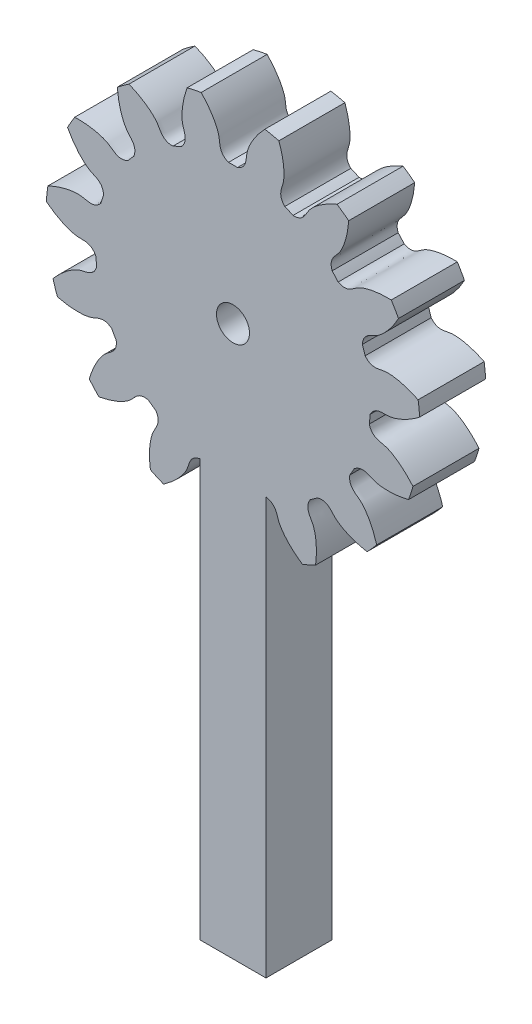
SolidWorks part; units mm, degrees
ref_plane "前视基准面" through (0, 0, 0) normal (0, 0, 1) x (1, 0, 0)
ref_plane "上视基准面" through (0, 0, 0) normal (0, 1, 0) x (1, 0, 0)
ref_plane "右视基准面" through (0, 0, 0) normal (1, 0, 0) x (0, 0, -1)
sketch "草图1" plane through (0, 0, 0) normal (0, 0, 1) x (1, 0, 0)
  circle A0 centre (0, 0) radius 17
extrude "凸台-拉伸1" add sketch "草图1" along normal blind 30
ref_axis "基准轴1" through (0, 0, -1.5) along (0, 0, 1)
sketch "草图2" plane through (0, 0, 0) normal (0, 0, 1) x (1, 0, 0)
  line L0 (0, 0) -> (0, 17) construction
  circle A0 centre (0, 0) radius 17 construction
  arc A1 (0.4086, 12.4933) -> (-0.4086, 12.4933) centre (0, 0) ccw
  arc A2 (6.4937, 19.2719) -> (-6.4937, 19.2719) centre (0, 0) ccw
  spline S0 degree 3 poles (0.4086, 12.4933) (1.3144, 12.8688) (1.1442, 13.5727) (1.3025, 14.217) (1.3149, 14.2633) (1.3297, 14.3148) (1.3472, 14.3713) (1.3676, 14.4329) (1.3912, 14.4993) (1.418, 14.5705) (1.4484, 14.6465) (1.4824, 14.7269) (1.5204, 14.8119) (1.5624, 14.9011) (1.6088, 14.9946) (1.6596, 15.0921) (1.715, 15.1935) (1.7753, 15.2987) (1.8405, 15.4075) (1.9109, 15.5198) (1.9867, 15.6353) (2.0679, 15.754) (2.1547, 15.8755) (2.2473, 15.9999) (2.3459, 16.1268) (2.4505, 16.2561) (2.5613, 16.3877) (2.6784, 16.5212) (2.802, 16.6565) (2.9322, 16.7934) (3.069, 16.9316) (3.2126, 17.0711) (3.3631, 17.2115) (3.5206, 17.3526) (3.6851, 17.4942) (3.8568, 17.6361) (4.0357, 17.778) (4.2219, 17.9197) (4.4154, 18.061) (4.6163, 18.2017) (4.8247, 18.3414) (5.0406, 18.48) (5.2641, 18.6172) (5.4951, 18.7527) (5.7336, 18.8864) (6.0652, 19.0635) (6.3203, 19.1901) (6.4937, 19.2719) knots 0 0 0 0 0.202473 0.206979 0.212085 0.217793 0.224101 0.23101 0.23852 0.24663 0.255341 0.264653 0.274566 0.285079 0.296194 0.307909 0.320225 0.333141 0.346659 0.360777 0.375496 0.390816 0.406736 0.423257 0.440379 0.458102 0.476426 0.49535 0.514875 0.535001 0.555728 0.577055 0.598984 0.621513 0.644642 0.668373 0.692704 0.717636 0.743169 0.769303 0.796037 0.823373 0.851309 0.879845 0.908983 0.938721 1 1 1 1
  spline S1 degree 3 poles (-0.4086, 12.4933) (-1.3144, 12.8688) (-1.1442, 13.5727) (-1.3025, 14.217) (-1.3149, 14.2633) (-1.3297, 14.3148) (-1.3472, 14.3713) (-1.3676, 14.4329) (-1.3912, 14.4993) (-1.418, 14.5705) (-1.4484, 14.6465) (-1.4824, 14.7269) (-1.5204, 14.8119) (-1.5624, 14.9011) (-1.6088, 14.9946) (-1.6596, 15.0921) (-1.715, 15.1935) (-1.7753, 15.2987) (-1.8405, 15.4075) (-1.9109, 15.5198) (-1.9867, 15.6353) (-2.0679, 15.754) (-2.1547, 15.8755) (-2.2473, 15.9999) (-2.3459, 16.1268) (-2.4505, 16.2561) (-2.5613, 16.3877) (-2.6784, 16.5212) (-2.802, 16.6565) (-2.9322, 16.7934) (-3.069, 16.9316) (-3.2126, 17.0711) (-3.3631, 17.2115) (-3.5206, 17.3526) (-3.6851, 17.4942) (-3.8568, 17.6361) (-4.0357, 17.778) (-4.2219, 17.9197) (-4.4154, 18.061) (-4.6163, 18.2017) (-4.8247, 18.3414) (-5.0406, 18.48) (-5.2641, 18.6172) (-5.4951, 18.7527) (-5.7336, 18.8864) (-6.0652, 19.0635) (-6.3203, 19.1901) (-6.4937, 19.2719) knots 0 0 0 0 0.202473 0.206979 0.212085 0.217793 0.224101 0.23101 0.23852 0.24663 0.255341 0.264653 0.274566 0.285079 0.296194 0.307909 0.320225 0.333141 0.346659 0.360777 0.375496 0.390816 0.406736 0.423257 0.440379 0.458102 0.476426 0.49535 0.514875 0.535001 0.555728 0.577055 0.598984 0.621513 0.644642 0.668373 0.692704 0.717636 0.743169 0.769303 0.796037 0.823373 0.851309 0.879845 0.908983 0.938721 1 1 1 1
extrude "切除-拉伸1" cut sketch "草图2" along normal through all
pattern_circular "阵列(圆周)1" count 15 every 24 about axis through (0, 0, -1.5) along (0, 0, 1) of "切除-拉伸1"
sketch "草图3" plane through (0, 0, 0) normal (0, 0, 1) x (1, 0, 0)
  circle A0 centre (0, 0) radius 15 construction
  dimension "Dn" = 30
sketch "草图4" plane through (0, 0, 30) normal (0, 0, 1) x (1, 0, 0)
  arc A30 (-4.7082, 11.5794) -> (-5.4547, 11.247) centre (0, 0) ccw
  arc A31 (-9.4567, 14.127) -> (-10.5132, 13.3593) centre (0, 0) ccw
  arc A32 (-9.011, 8.6633) -> (-9.5577, 8.056) centre (0, 0) ccw
  arc A33 (-14.3851, 9.0592) -> (-15.0381, 7.9282) centre (0, 0) ccw
  arc A34 (-11.7556, 4.2492) -> (-12.0081, 3.4721) centre (0, 0) ccw
  arc A35 (-16.8261, 2.4251) -> (-16.9627, 1.1263) centre (0, 0) ccw
  arc A36 (-12.4676, -0.8996) -> (-12.3822, -1.7122) centre (0, 0) ccw
  arc A37 (-16.3578, -4.6284) -> (-15.9542, -5.8704) centre (0, 0) ccw
  arc A38 (-11.0238, -5.8928) -> (-10.6152, -6.6005) centre (0, 0) ccw
  arc A39 (-13.0611, -10.8816) -> (-12.1872, -11.8521) centre (0, 0) ccw
  arc A40 (-7.6739, -9.8672) -> (-7.0128, -10.3475) centre (0, 0) ccw
  arc A41 (-7.5059, -15.2532) -> (-6.3129, -15.7844) centre (0, 0) ccw
  arc A42 (-2.9971, -12.1354) -> (-2.1979, -12.3053) centre (0, 0) ccw
  arc A43 (-0.653, -16.9875) -> (0.653, -16.9875) centre (0, 0) ccw
  arc A44 (2.1979, -12.3053) -> (2.9971, -12.1354) centre (0, 0) ccw
  arc A45 (6.3129, -15.7844) -> (7.5059, -15.2532) centre (0, 0) ccw
  arc A46 (7.0128, -10.3475) -> (7.6739, -9.8672) centre (0, 0) ccw
  arc A47 (12.1872, -11.8521) -> (13.0611, -10.8816) centre (0, 0) ccw
  arc A48 (10.6152, -6.6005) -> (11.0238, -5.8928) centre (0, 0) ccw
  arc A49 (15.9542, -5.8704) -> (16.3578, -4.6284) centre (0, 0) ccw
  arc A50 (12.3822, -1.7122) -> (12.4676, -0.8996) centre (0, 0) ccw
  arc A51 (16.9627, 1.1263) -> (16.8261, 2.4251) centre (0, 0) ccw
  arc A52 (12.0081, 3.4721) -> (11.7556, 4.2492) centre (0, 0) ccw
  arc A53 (15.0381, 7.9282) -> (14.3851, 9.0592) centre (0, 0) ccw
  arc A54 (9.5577, 8.056) -> (9.011, 8.6633) centre (0, 0) ccw
  arc A55 (10.5132, 13.3593) -> (9.4567, 14.127) centre (0, 0) ccw
  arc A56 (5.4547, 11.247) -> (4.7082, 11.5794) centre (0, 0) ccw
  arc A57 (4.1706, 16.4805) -> (2.8932, 16.752) centre (0, 0) ccw
  arc A58 (0.4086, 12.4933) -> (-0.4086, 12.4933) centre (0, 0) ccw
  arc A59 (-2.8932, 16.752) -> (-4.1706, 16.4805) centre (0, 0) ccw
  arc A60 (-4.7082, 11.5794) -> (-5.4547, 11.247) centre (0, 0) ccw
  arc A61 (-9.4567, 14.127) -> (-10.5132, 13.3593) centre (0, 0) ccw
  arc A62 (-9.011, 8.6633) -> (-9.5577, 8.056) centre (0, 0) ccw
  arc A63 (-14.3851, 9.0592) -> (-15.0381, 7.9282) centre (0, 0) ccw
  arc A64 (-11.7556, 4.2492) -> (-12.0081, 3.4721) centre (0, 0) ccw
  arc A65 (-16.8261, 2.4251) -> (-16.9627, 1.1263) centre (0, 0) ccw
  arc A66 (-12.4676, -0.8996) -> (-12.3822, -1.7122) centre (0, 0) ccw
  arc A67 (-16.3578, -4.6284) -> (-15.9542, -5.8704) centre (0, 0) ccw
  arc A68 (-11.0238, -5.8928) -> (-10.6152, -6.6005) centre (0, 0) ccw
  arc A69 (-13.0611, -10.8816) -> (-12.1872, -11.8521) centre (0, 0) ccw
  arc A70 (-7.6739, -9.8672) -> (-7.0128, -10.3475) centre (0, 0) ccw
  arc A71 (-7.5059, -15.2532) -> (-6.3129, -15.7844) centre (0, 0) ccw
  arc A72 (-2.9971, -12.1354) -> (-2.1979, -12.3053) centre (0, 0) ccw
  arc A73 (-0.653, -16.9875) -> (0.653, -16.9875) centre (0, 0) ccw
  arc A74 (2.1979, -12.3053) -> (2.9971, -12.1354) centre (0, 0) ccw
  arc A75 (6.3129, -15.7844) -> (7.5059, -15.2532) centre (0, 0) ccw
  arc A76 (7.0128, -10.3475) -> (7.6739, -9.8672) centre (0, 0) ccw
  arc A77 (12.1872, -11.8521) -> (13.0611, -10.8816) centre (0, 0) ccw
  arc A78 (10.6152, -6.6005) -> (11.0238, -5.8928) centre (0, 0) ccw
  arc A79 (15.9542, -5.8704) -> (16.3578, -4.6284) centre (0, 0) ccw
  arc A80 (12.3822, -1.7122) -> (12.4676, -0.8996) centre (0, 0) ccw
  arc A81 (16.9627, 1.1263) -> (16.8261, 2.4251) centre (0, 0) ccw
  arc A82 (12.0081, 3.4721) -> (11.7556, 4.2492) centre (0, 0) ccw
  arc A83 (15.0381, 7.9282) -> (14.3851, 9.0592) centre (0, 0) ccw
  arc A84 (9.5577, 8.056) -> (9.011, 8.6633) centre (0, 0) ccw
  arc A85 (10.5132, 13.3593) -> (9.4567, 14.127) centre (0, 0) ccw
  arc A86 (5.4547, 11.247) -> (4.7082, 11.5794) centre (0, 0) ccw
  arc A87 (4.1706, 16.4805) -> (2.8932, 16.752) centre (0, 0) ccw
  arc A88 (0.4086, 12.4933) -> (-0.4086, 12.4933) centre (0, 0) ccw
  arc A89 (-2.8932, 16.752) -> (-4.1706, 16.4805) centre (0, 0) ccw
  spline S30 degree 3 poles (3089.1595, 2545.0128) (-48.0651, -41.2526) (-1.4026, 5.2781) (-6.9834, 12.4722) (-7.0266, 12.5244) (-7.0761, 12.5809) (-7.1369, 12.6476) (-7.2252, 12.7386) (-7.3478, 12.8552) (-7.4919, 12.9818) (-7.6584, 13.1167) (-7.8482, 13.2583) (-8.0622, 13.405) (-8.3009, 13.555) (-8.565, 13.7067) (-8.8549, 13.858) (-42.0056, 29.516) (-165.8302, -157.3856) (3462.6996, 1998.8009) knots -2.221696 -2.221696 -2.221696 -2.221696 0.673329 0.677835 0.688649 0.694957 0.701866 0.717486 0.735509 0.755935 0.778765 0.803997 0.831633 0.861672 0.894113 0.928958 0.966206 12.611489 12.611489 12.611489 12.611489 only from (-5.4547, 11.247) to (-9.4567, 14.127)
  spline S31 degree 3 poles (-2967.0957, -2679.8675) (198.3354, 111.6925) (-15.6965, 48.1718) (-10.4174, 12.5396) (-10.3587, 12.2293) (-10.2927, 11.9436) (-10.2213, 11.6825) (-10.1464, 11.4459) (-10.0697, 11.2338) (-10.0041, 11.0727) (-9.9413, 10.931) (-9.8926, 10.8293) (-9.8442, 10.7358) (-9.8106, 10.6738) (-9.7785, 10.6175) (-9.74, 10.5529) (-9.7038, 10.4958) (-4.5863, 2.965) (54.0858, 32.9645) (-3374.9897, -2151.4722) knots -11.389987 -11.389987 -11.389987 -11.389987 0.052718 0.088765 0.122408 0.153648 0.182485 0.208919 0.23295 0.254578 0.264491 0.282514 0.290624 0.298134 0.305043 0.311351 0.322165 0.326671 3.221678 3.221678 3.221678 3.221678 only from (-10.5132, 13.3593) to (-9.011, 8.6633)
  spline S32 degree 3 poles (1786.9376, 3581.4592) (-27.1307, -57.236) (-3.4282, 4.2513) (-11.4526, 8.5535) (-11.5132, 8.5836) (-11.5815, 8.6151) (-11.6641, 8.6513) (-11.7819, 8.6985) (-11.9413, 8.7552) (-12.1243, 8.8122) (-12.3313, 8.8677) (-12.5623, 8.9199) (-12.8175, 8.9669) (-13.0966, 9.0069) (-13.3995, 9.038) (-13.7259, 9.0583) (-50.3793, 9.879) (-87.479, -211.2281) (2350.348, 3234.4023) knots -2.221696 -2.221696 -2.221696 -2.221696 0.673329 0.677835 0.688649 0.694957 0.701866 0.717486 0.735509 0.755935 0.778765 0.803997 0.831633 0.861672 0.894113 0.928958 0.966206 12.611489 12.611489 12.611489 12.611489 only from (-9.5577, 8.056) to (-14.3851, 9.0592)
  spline S33 degree 3 poles (-1620.5765, -3655.0073) (135.759, 182.7064) (-33.9327, 37.6228) (-14.6171, 7.2183) (-14.4372, 6.9587) (-14.2607, 6.7246) (-14.0893, 6.5151) (-13.9246, 6.3295) (-13.7683, 6.1669) (-13.6429, 6.0464) (-13.5278, 5.9425) (-13.442, 5.8694) (-13.3598, 5.8036) (-13.3039, 5.7607) (-13.2516, 5.7223) (-13.1902, 5.6789) (-13.1339, 5.6415) (-5.3958, 0.8433) (36.002, 52.1132) (-2208.1239, -3338.1997) knots -11.389987 -11.389987 -11.389987 -11.389987 0.052718 0.088765 0.122408 0.153648 0.182485 0.208919 0.23295 0.254578 0.264491 0.282514 0.290624 0.298134 0.305043 0.311351 0.322165 0.326671 3.221678 3.221678 3.221678 3.221678 only from (-15.0381, 7.9282) to (-11.7556, 4.2492)
  spline S34 degree 3 poles (175.7381, 3998.6388) (-1.5051, -63.3227) (-4.8609, 2.4894) (-13.9415, 3.1558) (-14.0091, 3.1587) (-14.0843, 3.1597) (-14.1745, 3.1591) (-14.3013, 3.1544) (-14.47, 3.1414) (-14.6604, 3.119) (-14.872, 3.0855) (-15.1043, 3.0392) (-15.3565, 2.9783) (-15.6277, 2.9013) (-15.9171, 2.8065) (-16.2236, 2.6924) (-50.0419, -11.4661) (5.9982, -228.5474) (831.5998, 3910.7461) knots -2.221696 -2.221696 -2.221696 -2.221696 0.673329 0.677835 0.688649 0.694957 0.701866 0.717486 0.735509 0.755935 0.778765 0.803997 0.831633 0.861672 0.894113 0.928958 0.966206 12.611489 12.611489 12.611489 12.611489 only from (-12.0081, 3.4721) to (-16.8261, 2.4251)
  spline S35 degree 3 poles (6.1551, -3998.1632) (49.7086, 222.1288) (-46.3016, 20.5684) (-16.2893, 0.649) (-16.0194, 0.485) (-15.763, 0.3428) (-15.5212, 0.2212) (-15.2952, 0.1186) (-15.0863, 0.0336) (-14.9227, -0.0254) (-14.7753, -0.0735) (-14.6671, -0.1054) (-14.5653, -0.132) (-14.4968, -0.1485) (-14.4334, -0.1624) (-14.3597, -0.177) (-14.293, -0.1883) (-5.2723, -1.4243) (11.6931, 62.2511) (-659.4535, -3947.7221) knots -11.389987 -11.389987 -11.389987 -11.389987 0.052718 0.088765 0.122408 0.153648 0.182485 0.208919 0.23295 0.254578 0.264491 0.282514 0.290624 0.298134 0.305043 0.311351 0.322165 0.326671 3.221678 3.221678 3.221678 3.221678 only from (-16.9627, 1.1263) to (-12.4676, -0.8996)
  spline S36 degree 3 poles (-1465.8482, 3724.4174) (24.3807, -58.4604) (-5.4532, 0.297) (-14.0198, -2.7875) (-14.0827, -2.8124) (-14.1518, -2.8421) (-14.234, -2.8793) (-14.3479, -2.9352) (-14.4967, -3.0157) (-14.6615, -3.1136) (-14.8413, -3.2303) (-15.0346, -3.3671) (-15.2402, -3.5252) (-15.4567, -3.7059) (-15.6825, -3.9102) (-15.9161, -4.1391) (-41.0519, -30.8287) (98.4382, -206.3487) (-830.9396, 3910.8865) knots -2.221696 -2.221696 -2.221696 -2.221696 0.673329 0.677835 0.688649 0.694957 0.701866 0.717486 0.735509 0.755935 0.778765 0.803997 0.831633 0.861672 0.894113 0.928958 0.966206 12.611489 12.611489 12.611489 12.611489 only from (-12.3822, -1.7122) to (-16.3578, -4.6284)
  spline S37 degree 3 poles (1631.8224, -3650.0003) (-44.9369, 223.143) (-50.6646, -0.0424) (-15.145, -6.0326) (-14.8318, -6.0726) (-14.5396, -6.0982) (-14.2692, -6.111) (-14.0211, -6.1128) (-13.7957, -6.1054) (-13.6222, -6.0928) (-13.468, -6.0768) (-13.3562, -6.062) (-13.2524, -6.0449) (-13.1831, -6.032) (-13.1196, -6.0189) (-13.0462, -6.0023) (-12.9807, -5.9855) (-4.2372, -3.4456) (-14.6376, 61.6252) (1003.2425, -3874.6475) knots -11.389987 -11.389987 -11.389987 -11.389987 0.052718 0.088765 0.122408 0.153648 0.182485 0.208919 0.23295 0.254578 0.264491 0.282514 0.290624 0.298134 0.305043 0.311351 0.322165 0.326671 3.221678 3.221678 3.221678 3.221678 only from (-15.9542, -5.8704) to (-11.0238, -5.8928)
  spline S38 degree 3 poles (-2853.976, 2806.2104) (46.0508, -43.4897) (-5.1025, -1.9467) (-11.6739, -8.2489) (-11.7213, -8.2972) (-11.7723, -8.3524) (-11.8323, -8.4198) (-11.9136, -8.5172) (-12.0168, -8.6513) (-12.1276, -8.8078) (-12.2443, -8.9875) (-12.3653, -9.1911) (-12.4888, -9.4192) (-12.6131, -9.6723) (-12.7363, -9.9508) (-12.8565, -10.255) (-24.9636, -44.8607) (173.8574, -148.4705) (-2349.8019, 3234.799) knots -2.221696 -2.221696 -2.221696 -2.221696 0.673329 0.677835 0.688649 0.694957 0.701866 0.717486 0.735509 0.755935 0.778765 0.803997 0.831633 0.861672 0.894113 0.928958 0.966206 12.611489 12.611489 12.611489 12.611489 only from (-10.6152, -6.6005) to (-13.0611, -10.8816)
  spline S39 degree 3 poles (2975.3328, -2670.7192) (-131.8123, 185.5738) (-46.2672, -20.6458) (-11.382, -11.6711) (-11.0795, -11.5803) (-10.8023, -11.4848) (-10.5501, -11.3865) (-10.3226, -11.2872) (-10.1197, -11.1888) (-9.9664, -11.1067) (-9.832, -11.0294) (-9.7359, -10.9703) (-9.648, -10.9125) (-9.5899, -10.8726) (-9.5372, -10.8348) (-9.477, -10.7898) (-9.4239, -10.7477) (-2.4694, -4.8712) (-38.4374, 50.3438) (2492.4687, -3131.6111) knots -11.389987 -11.389987 -11.389987 -11.389987 0.052718 0.088765 0.122408 0.153648 0.182485 0.208919 0.23295 0.254578 0.264491 0.282514 0.290624 0.298134 0.305043 0.311351 0.322165 0.326671 3.221678 3.221678 3.221678 3.221678 only from (-12.1872, -11.8521) to (-7.6739, -9.8672)
  spline S40 degree 3 poles (-3748.6254, 1402.7842) (59.7584, -20.9993) (-3.8696, -3.8538) (-7.3095, -12.2839) (-7.3331, -12.3474) (-7.3573, -12.4185) (-7.3847, -12.5045) (-7.4193, -12.6266) (-7.4591, -12.791) (-7.4966, -12.979) (-7.5302, -13.1907) (-7.5579, -13.4259) (-7.578, -13.6845) (-7.5886, -13.9663) (-7.5878, -14.2708) (-7.574, -14.5976) (-4.5589, -51.1359) (219.215, -64.9204) (-3462.3621, 1999.3854) knots -2.221696 -2.221696 -2.221696 -2.221696 0.673329 0.677835 0.688649 0.694957 0.701866 0.717486 0.735509 0.755935 0.778765 0.803997 0.831633 0.861672 0.894113 0.928958 0.966206 12.611489 12.611489 12.611489 12.611489 only from (-7.0128, -10.3475) to (-7.5059, -15.2532)
  spline S41 degree 3 poles (3804.3812, -1229.6465) (-195.8962, 115.9172) (-33.8697, -37.6795) (-5.6509, -15.2915) (-5.4115, -15.0855) (-5.1971, -14.8855) (-5.0067, -14.6931) (-4.8393, -14.51) (-4.6939, -14.3375) (-4.5872, -14.2002) (-4.4959, -14.0749) (-4.4321, -13.9819) (-4.3754, -13.8932) (-4.3385, -13.8331) (-4.3057, -13.7772) (-4.2691, -13.7116) (-4.2377, -13.6516) (-0.2746, -5.4544) (-55.591, 30.3574) (3550.7245, -1847.0907) knots -11.389987 -11.389987 -11.389987 -11.389987 0.052718 0.088765 0.122408 0.153648 0.182485 0.208919 0.23295 0.254578 0.264491 0.282514 0.290624 0.298134 0.305043 0.311351 0.322165 0.326671 3.221678 3.221678 3.221678 3.221678 only from (-6.3129, -15.7844) to (-2.9971, -12.1354)
  spline S42 degree 3 poles (-3995.1035, -243.1962) (63.1332, 5.1221) (-1.9676, -5.0945) (-1.6813, -14.195) (-1.677, -14.2625) (-1.6702, -14.3374) (-1.6602, -14.4271) (-1.6422, -14.5527) (-1.6116, -14.719) (-1.5695, -14.9061) (-1.514, -15.1131) (-1.4437, -15.3393) (-1.3568, -15.5837) (-1.2519, -15.8454) (-1.1274, -16.1233) (-0.9818, -16.4162) (16.6341, -48.5692) (226.6684, 29.855) (-3976.2485, 418.2599) knots -2.221696 -2.221696 -2.221696 -2.221696 0.673329 0.677835 0.688649 0.694957 0.701866 0.717486 0.735509 0.755935 0.778765 0.803997 0.831633 0.861672 0.894113 0.928958 0.966206 12.611489 12.611489 12.611489 12.611489 only from (-2.1979, -12.3053) to (-0.653, -16.9875)
  spline S43 degree 3 poles (3975.6174, 424.0432) (-226.1079, 26.2175) (-15.6159, -48.198) (1.0573, -16.2679) (1.1922, -15.9824) (1.3067, -15.7124) (1.4024, -15.4592) (1.4808, -15.2238) (1.5435, -15.0071) (1.5851, -14.8383) (1.6176, -14.6867) (1.638, -14.5758) (1.6538, -14.4717) (1.663, -14.4018) (1.6702, -14.3374) (1.677, -14.2625) (1.6813, -14.195) (1.9676, -5.0946) (-63.1324, 5.122) (3995.0277, -243.1916) knots -11.389987 -11.389987 -11.389987 -11.389987 0.052718 0.088765 0.122408 0.153648 0.182485 0.208919 0.23295 0.254578 0.264491 0.282514 0.290624 0.298134 0.305043 0.311351 0.322165 0.326671 3.221678 3.221678 3.221678 3.221678 only from (0.653, -16.9875) to (2.1979, -12.3053)
  spline S44 degree 3 poles (-3550.7918, -1847.1258) (55.5917, 30.3579) (0.2746, -5.4544) (4.2377, -13.6516) (4.2691, -13.7116) (4.3057, -13.7772) (4.3513, -13.855) (4.4189, -13.9625) (4.5145, -14.102) (4.6291, -14.2557) (4.7639, -14.4223) (4.9202, -14.6003) (5.0989, -14.7883) (5.3012, -14.9847) (5.528, -15.1879) (5.7802, -15.3963) (34.9509, -37.6045) (194.9288, 119.4683) (-3802.6054, -1235.1865) knots -2.221696 -2.221696 -2.221696 -2.221696 0.673329 0.677835 0.688649 0.694957 0.701866 0.717486 0.735509 0.755935 0.778765 0.803997 0.831633 0.861672 0.894113 0.928958 0.966206 12.611489 12.611489 12.611489 12.611489 only from (2.9971, -12.1354) to (6.3129, -15.7844)
  spline S45 degree 3 poles (3459.4333, 2004.4121) (-217.2235, -68.0155) (5.338, -50.3826) (7.5826, -14.4315) (7.5897, -14.1157) (7.5846, -13.8225) (7.569, -13.5523) (7.5449, -13.3054) (7.514, -13.0819) (7.4834, -12.9107) (7.4513, -12.759) (7.4249, -12.6494) (7.397, -12.5479) (7.377, -12.4803) (7.3573, -12.4185) (7.3331, -12.3474) (7.3095, -12.2839) (3.8697, -3.8538) (-59.7576, -20.999) (3748.5543, 1402.7576) knots -11.389987 -11.389987 -11.389987 -11.389987 0.052718 0.088765 0.122408 0.153648 0.182485 0.208919 0.23295 0.254578 0.264491 0.282514 0.290624 0.298134 0.305043 0.311351 0.322165 0.326671 3.221678 3.221678 3.221678 3.221678 only from (7.5059, -15.2532) to (7.0128, -10.3475)
  spline S46 degree 3 poles (-2492.516, -3131.6705) (38.4378, 50.3445) (2.4694, -4.8711) (9.4239, -10.7477) (9.477, -10.7898) (9.5372, -10.8348) (9.6105, -10.8873) (9.7159, -10.958) (9.86, -11.0466) (10.0272, -11.1405) (10.2181, -11.2378) (10.4333, -11.3368) (10.673, -11.4358) (10.9377, -11.533) (11.2276, -11.6264) (11.5427, -11.7142) (47.2244, -20.1376) (129.4842, 188.4244) (-2971.4573, -2675.058) knots -2.221696 -2.221696 -2.221696 -2.221696 0.673329 0.677835 0.688649 0.694957 0.701866 0.717486 0.735509 0.755935 0.778765 0.803997 0.831633 0.861672 0.894113 0.928958 0.966206 12.611489 12.611489 12.611489 12.611489 only from (7.6739, -9.8672) to (12.1872, -11.8521)
  spline S47 degree 3 poles (2345.0818, 3238.1998) (-170.7791, -150.488) (25.369, -43.8556) (12.7969, -10.0997) (12.6749, -9.8084) (12.551, -9.5426) (12.4269, -9.302) (12.3044, -9.0863) (12.1853, -8.8947) (12.0877, -8.7508) (11.9967, -8.6252) (11.9279, -8.5358) (11.8612, -8.4545) (11.8154, -8.4009) (11.7723, -8.3524) (11.7213, -8.2972) (11.6739, -8.2489) (5.1026, -1.9467) (-46.0502, -43.4892) (2853.9219, 2806.1572) knots -11.389987 -11.389987 -11.389987 -11.389987 0.052718 0.088765 0.122408 0.153648 0.182485 0.208919 0.23295 0.254578 0.264491 0.282514 0.290624 0.298134 0.305043 0.311351 0.322165 0.326671 3.221678 3.221678 3.221678 3.221678 only from (13.0611, -10.8816) to (10.6152, -6.6005)
  spline S48 degree 3 poles (-1003.2615, -3874.721) (14.6378, 61.626) (4.2371, -3.4456) (12.9807, -5.9855) (13.0462, -6.0023) (13.1196, -6.0189) (13.2079, -6.0371) (13.3329, -6.0589) (13.5006, -6.0812) (13.6915, -6.0989) (13.9055, -6.1101) (14.1424, -6.1131) (14.4017, -6.106) (14.683, -6.0871) (14.9858, -6.0545) (15.3093, -6.0066) (51.3323, 0.8113) (41.6506, 224.8002) (-1626.5172, -3652.3876) knots -2.221696 -2.221696 -2.221696 -2.221696 0.673329 0.677835 0.688649 0.694957 0.701866 0.717486 0.735509 0.755935 0.778765 0.803997 0.831633 0.861672 0.894113 0.928958 0.966206 12.611489 12.611489 12.611489 12.611489 only from (11.0238, -5.8928) to (15.9542, -5.8704)
  spline S49 degree 3 poles (825.2443, 3912.0734) (-94.8055, -206.9397) (41.0134, -29.7456) (15.7984, -4.0215) (15.5686, -3.805) (15.3472, -3.6127) (15.136, -3.4434) (14.9363, -3.2961) (14.7496, -3.1695) (14.6019, -3.0778) (14.4677, -3) (14.3685, -2.9464) (14.2745, -2.8991) (14.2109, -2.8688) (14.1518, -2.8421) (14.0827, -2.8124) (14.0198, -2.7875) (5.4532, 0.297) (-24.3803, -58.4597) (1465.8204, 3724.3468) knots -11.389987 -11.389987 -11.389987 -11.389987 0.052718 0.088765 0.122408 0.153648 0.182485 0.208919 0.23295 0.254578 0.264491 0.282514 0.290624 0.298134 0.305043 0.311351 0.322165 0.326671 3.221678 3.221678 3.221678 3.221678 only from (16.3578, -4.6284) to (12.3822, -1.7122)
  spline S50 degree 3 poles (659.466, -3947.797) (-11.6933, 62.2519) (5.2723, -1.4243) (14.293, -0.1883) (14.3597, -0.177) (14.4334, -0.1624) (14.5216, -0.1431) (14.6446, -0.1121) (14.8069, -0.0642) (14.9885, -0.0027) (15.1886, 0.074) (15.4061, 0.1676) (15.6401, 0.2795) (15.8894, 0.4113) (16.1528, 0.5642) (16.4289, 0.7396) (46.5644, 21.6199) (-53.3848, 222.306) (-0.3375, -3998.1863) knots -2.221696 -2.221696 -2.221696 -2.221696 0.673329 0.677835 0.688649 0.694957 0.701866 0.717486 0.735509 0.755935 0.778765 0.803997 0.831633 0.861672 0.894113 0.928958 0.966206 12.611489 12.611489 12.611489 12.611489 only from (12.4676, -0.8996) to (16.9627, 1.1263)
  spline S51 degree 3 poles (-837.2855, 3909.514) (-2.4392, -227.6097) (49.5662, -10.4923) (16.0683, 2.752) (15.7702, 2.8562) (15.4898, 2.942) (15.228, 3.0107) (14.9856, 3.064) (14.7636, 3.1037) (14.5913, 3.1275) (14.4372, 3.1439) (14.3247, 3.1526) (14.2196, 3.1574) (14.1491, 3.1593) (14.0843, 3.1597) (14.0091, 3.1587) (13.9415, 3.1558) (4.861, 2.4894) (1.5052, -63.3219) (-175.7348, 3998.563) knots -11.389987 -11.389987 -11.389987 -11.389987 0.052718 0.088765 0.122408 0.153648 0.182485 0.208919 0.23295 0.254578 0.264491 0.282514 0.290624 0.298134 0.305043 0.311351 0.322165 0.326671 3.221678 3.221678 3.221678 3.221678 only from (16.8261, 2.4251) to (12.0081, 3.4721)
  spline S52 degree 3 poles (2208.1658, -3338.263) (-36.0025, 52.1139) (5.3958, 0.8432) (13.1339, 5.6415) (13.1902, 5.6789) (13.2516, 5.7223) (13.3243, 5.7758) (13.4241, 5.8541) (13.5529, 5.9638) (13.6938, 6.0939) (13.8453, 6.2454) (14.006, 6.4194) (14.1743, 6.6168) (14.3485, 6.8385) (14.5269, 7.0853) (14.7077, 7.3578) (33.7451, 38.6902) (-139.1894, 181.3731) (1625.9006, -3652.6622) knots -2.221696 -2.221696 -2.221696 -2.221696 0.673329 0.677835 0.688649 0.694957 0.701866 0.717486 0.735509 0.755935 0.778765 0.803997 0.831633 0.861672 0.894113 0.928958 0.966206 12.611489 12.611489 12.611489 12.611489 only from (11.7556, 4.2492) to (15.0381, 7.9282)
  spline S53 degree 3 poles (-2355.0409, 3230.9641) (90.3489, -208.9239) (49.5486, 10.5752) (13.5598, 9.0496) (13.2451, 9.0236) (12.954, 8.9879) (12.6869, 8.9442) (12.4438, 8.8943) (12.2248, 8.8403) (12.0578, 8.7919) (11.9103, 8.7442) (11.804, 8.7064) (11.706, 8.6681) (11.6409, 8.6411) (11.5815, 8.6151) (11.5132, 8.5836) (11.4526, 8.5535) (3.4282, 4.2513) (27.1304, -57.2352) (-1786.9038, 3581.3913) knots -11.389987 -11.389987 -11.389987 -11.389987 0.052718 0.088765 0.122408 0.153648 0.182485 0.208919 0.23295 0.254578 0.264491 0.282514 0.290624 0.298134 0.305043 0.311351 0.322165 0.326671 3.221678 3.221678 3.221678 3.221678 only from (14.3851, 9.0592) to (9.5577, 8.056)
  spline S54 degree 3 poles (3375.0538, -2151.513) (-54.0865, 32.9648) (4.5863, 2.965) (9.7038, 10.4958) (9.74, 10.5529) (9.7785, 10.6175) (9.8231, 10.6959) (9.8824, 10.8081) (9.9555, 10.9607) (10.0313, 11.1368) (10.1081, 11.3368) (10.1842, 11.5611) (10.2576, 11.8099) (10.3265, 12.0833) (10.3891, 12.3814) (10.4435, 12.7039) (15.091, 49.0706) (-200.9269, 109.0791) (2971.0056, -2675.5596) knots -2.221696 -2.221696 -2.221696 -2.221696 0.673329 0.677835 0.688649 0.694957 0.701866 0.717486 0.735509 0.755935 0.778765 0.803997 0.831633 0.861672 0.894113 0.928958 0.966206 12.611489 12.611489 12.611489 12.611489 only from (9.011, 8.6633) to (10.5132, 13.3593)
  spline S55 degree 3 poles (-3465.5884, 1993.7511) (167.5149, -154.1133) (40.9636, 29.8142) (8.7067, 13.7825) (8.4297, 13.6308) (8.1784, 13.4797) (7.9521, 13.3311) (7.7503, 13.1867) (7.5723, 13.0483) (7.4394, 12.9362) (7.324, 12.8326) (7.2423, 12.7548) (7.1683, 12.6799) (7.1198, 12.6288) (7.0761, 12.5809) (7.0266, 12.5244) (6.9834, 12.4722) (1.4027, 5.2781) (48.0645, -41.2521) (-3089.1009, 2544.9645) knots -11.389987 -11.389987 -11.389987 -11.389987 0.052718 0.088765 0.122408 0.153648 0.182485 0.208919 0.23295 0.254578 0.264491 0.282514 0.290624 0.298134 0.305043 0.311351 0.322165 0.326671 3.221678 3.221678 3.221678 3.221678 only from (9.4567, 14.127) to (5.4547, 11.247)
  spline S56 degree 3 poles (3958.3642, -592.7469) (-62.8185, 8.1159) (2.9838, 4.5741) (4.5958, 13.5352) (4.6057, 13.6022) (4.6146, 13.6768) (4.6235, 13.7666) (4.632, 13.8932) (4.6367, 14.0623) (4.6343, 14.254) (4.6231, 14.468) (4.6014, 14.7039) (4.5672, 14.961) (4.519, 15.2388) (4.4549, 15.5366) (4.3734, 15.8533) (-6.1725, 50.9663) (-227.9224, 17.9244) (3802.3968, -1235.8285) knots -2.221696 -2.221696 -2.221696 -2.221696 0.673329 0.677835 0.688649 0.694957 0.701866 0.717486 0.735509 0.755935 0.778765 0.803997 0.831633 0.861672 0.894113 0.928958 0.966206 12.611489 12.611489 12.611489 12.611489 only from (4.7082, 11.5794) to (4.1706, 16.4805)
  spline S57 degree 3 poles (-3976.9042, 411.8005) (215.716, -72.6551) (25.2956, 43.898) (2.3481, 16.1323) (2.1568, 15.881) (1.9886, 15.6408) (1.8424, 15.413) (1.7167, 15.199) (1.6104, 15.0001) (1.5346, 14.8436) (1.4713, 14.7021) (1.4283, 14.5978) (1.3912, 14.4993) (1.3676, 14.4329) (1.3472, 14.3713) (1.325, 14.2995) (1.3068, 14.2343) (-0.8654, 5.3923) (60.6878, -18.136) (-3857.1644, 1068.4902) knots -11.389987 -11.389987 -11.389987 -11.389987 0.052718 0.088765 0.122408 0.153648 0.182485 0.208919 0.23295 0.254578 0.264491 0.282514 0.290624 0.298134 0.305043 0.311351 0.322165 0.326671 3.221678 3.221678 3.221678 3.221678 only from (2.8932, 16.752) to (0.4086, 12.4933)
  spline S58 degree 3 poles (3857.2375, 1068.5105) (-60.6886, -18.1363) (0.8654, 5.3923) (-1.3068, 14.2343) (-1.325, 14.2995) (-1.3472, 14.3713) (-1.3756, 14.457) (-1.4193, 14.5761) (-1.4839, 14.7325) (-1.564, 14.9067) (-1.6612, 15.0976) (-1.7771, 15.3042) (-1.9128, 15.5252) (-2.0699, 15.7594) (-2.2495, 16.0053) (-2.4528, 16.2616) (-26.3687, 44.0495) (-215.5079, -76.3296) (3976.3191, 417.5886) knots -2.221696 -2.221696 -2.221696 -2.221696 0.673329 0.677835 0.688649 0.694957 0.701866 0.717486 0.735509 0.755935 0.778765 0.803997 0.831633 0.861672 0.894113 0.928958 0.966206 12.611489 12.611489 12.611489 12.611489 only from (-0.4086, 12.4933) to (-2.8932, 16.752)
  spline S59 degree 3 poles (-3800.5771, -1241.3542) (226.6178, 21.3659) (5.2538, 50.3915) (-4.4165, 15.6926) (-4.489, 15.3853) (-4.545, 15.0974) (-4.5859, 14.8298) (-4.6137, 14.5833) (-4.6299, 14.3583) (-4.6355, 14.1845) (-4.6358, 14.0294) (-4.6327, 13.9167) (-4.6265, 13.8116) (-4.621, 13.7414) (-4.6146, 13.6768) (-4.6057, 13.6022) (-4.5958, 13.5352) (-2.9838, 4.5741) (62.8177, 8.1159) (-3958.2891, -592.7357) knots -11.389987 -11.389987 -11.389987 -11.389987 0.052718 0.088765 0.122408 0.153648 0.182485 0.208919 0.23295 0.254578 0.264491 0.282514 0.290624 0.298134 0.305043 0.311351 0.322165 0.326671 3.221678 3.221678 3.221678 3.221678 only from (-4.1706, 16.4805) to (-4.7082, 11.5794)
  spline S60 degree 3 poles (-5.4547, 11.247) (-6.435, 11.2216) (-6.5658, 11.9338) (-6.9834, 12.4722) (-7.0266, 12.5244) (-7.0761, 12.5809) (-7.1369, 12.6476) (-7.2252, 12.7386) (-7.3478, 12.8552) (-7.4919, 12.9818) (-7.6584, 13.1167) (-7.8482, 13.2583) (-8.0622, 13.405) (-8.3009, 13.555) (-8.565, 13.7067) (-8.8549, 13.858) (-9.1545, 13.9995) (-9.3588, 14.087) (-9.4567, 14.127) knots 0.470856 0.470856 0.470856 0.470856 0.673329 0.677835 0.688649 0.694957 0.701866 0.717486 0.735509 0.755935 0.778765 0.803997 0.831633 0.861672 0.894113 0.928958 0.966206 1 1 1 1
  spline S61 degree 3 poles (-10.5132, 13.3593) (-10.5011, 13.1949) (-10.4735, 12.9184) (-10.4174, 12.5396) (-10.3587, 12.2293) (-10.2927, 11.9436) (-10.2213, 11.6825) (-10.1464, 11.4459) (-10.0697, 11.2338) (-10.0041, 11.0727) (-9.9413, 10.931) (-9.8926, 10.8293) (-9.8442, 10.7358) (-9.8106, 10.6738) (-9.7785, 10.6175) (-9.74, 10.5529) (-9.7038, 10.4958) (-9.3208, 9.9322) (-8.6839, 9.5877) (-9.011, 8.6633) knots 0 0 0 0 0.052718 0.088765 0.122408 0.153648 0.182485 0.208919 0.23295 0.254578 0.264491 0.282514 0.290624 0.298134 0.305043 0.311351 0.322165 0.326671 0.529144 0.529144 0.529144 0.529144
  spline S62 degree 3 poles (-9.5577, 8.056) (-10.4429, 7.6341) (-10.8521, 8.2316) (-11.4526, 8.5535) (-11.5132, 8.5836) (-11.5815, 8.6151) (-11.6641, 8.6513) (-11.7819, 8.6985) (-11.9413, 8.7552) (-12.1243, 8.8122) (-12.3313, 8.8677) (-12.5623, 8.9199) (-12.8175, 8.9669) (-13.0966, 9.0069) (-13.3995, 9.038) (-13.7259, 9.0583) (-14.0572, 9.0658) (-14.2794, 9.0625) (-14.3851, 9.0592) knots 0.470856 0.470856 0.470856 0.470856 0.673329 0.677835 0.688649 0.694957 0.701866 0.717486 0.735509 0.755935 0.778765 0.803997 0.831633 0.861672 0.894113 0.928958 0.966206 1 1 1 1
  spline S63 degree 3 poles (-15.0381, 7.9282) (-14.9601, 7.7829) (-14.8225, 7.5416) (-14.6171, 7.2183) (-14.4372, 6.9587) (-14.2607, 6.7246) (-14.0893, 6.5151) (-13.9246, 6.3295) (-13.7683, 6.1669) (-13.6429, 6.0464) (-13.5278, 5.9425) (-13.442, 5.8694) (-13.3598, 5.8036) (-13.3039, 5.7607) (-13.2516, 5.7223) (-13.1902, 5.6789) (-13.1339, 5.6415) (-12.5548, 5.2824) (-11.8328, 5.2268) (-11.7556, 4.2492) knots 0 0 0 0 0.052718 0.088765 0.122408 0.153648 0.182485 0.208919 0.23295 0.254578 0.264491 0.282514 0.290624 0.298134 0.305043 0.311351 0.322165 0.326671 0.529144 0.529144 0.529144 0.529144
  spline S64 degree 3 poles (-12.0081, 3.4721) (-12.6452, 2.7266) (-13.262, 3.106) (-13.9415, 3.1558) (-14.0091, 3.1587) (-14.0843, 3.1597) (-14.1745, 3.1591) (-14.3013, 3.1544) (-14.47, 3.1414) (-14.6604, 3.119) (-14.872, 3.0855) (-15.1043, 3.0392) (-15.3565, 2.9783) (-15.6277, 2.9013) (-15.9171, 2.8065) (-16.2236, 2.6924) (-16.5292, 2.5644) (-16.731, 2.4711) (-16.8261, 2.4251) knots 0.470856 0.470856 0.470856 0.470856 0.673329 0.677835 0.688649 0.694957 0.701866 0.717486 0.735509 0.755935 0.778765 0.803997 0.831633 0.861672 0.894113 0.928958 0.966206 1 1 1 1
  spline S65 degree 3 poles (-16.9627, 1.1263) (-16.8323, 1.0252) (-16.6084, 0.8608) (-16.2893, 0.649) (-16.0194, 0.485) (-15.763, 0.3428) (-15.5212, 0.2212) (-15.2952, 0.1186) (-15.0863, 0.0336) (-14.9227, -0.0254) (-14.7753, -0.0735) (-14.6671, -0.1054) (-14.5653, -0.132) (-14.4968, -0.1485) (-14.4334, -0.1624) (-14.3597, -0.177) (-14.293, -0.1883) (-13.6179, -0.2808) (-12.9357, -0.0379) (-12.4676, -0.8996) knots 0 0 0 0 0.052718 0.088765 0.122408 0.153648 0.182485 0.208919 0.23295 0.254578 0.264491 0.282514 0.290624 0.298134 0.305043 0.311351 0.322165 0.326671 0.529144 0.529144 0.529144 0.529144
  spline S66 degree 3 poles (-12.3822, -1.7122) (-12.6609, -2.6524) (-13.3787, -2.5567) (-14.0198, -2.7875) (-14.0827, -2.8124) (-14.1518, -2.8421) (-14.234, -2.8793) (-14.3479, -2.9352) (-14.4967, -3.0157) (-14.6615, -3.1136) (-14.8413, -3.2303) (-15.0346, -3.3671) (-15.2402, -3.5252) (-15.4567, -3.7059) (-15.6825, -3.9102) (-15.9161, -4.1391) (-16.1432, -4.3803) (-16.2896, -4.5477) (-16.3578, -4.6284) knots 0.470856 0.470856 0.470856 0.470856 0.673329 0.677835 0.688649 0.694957 0.701866 0.717486 0.735509 0.755935 0.778765 0.803997 0.831633 0.861672 0.894113 0.928958 0.966206 1 1 1 1
  spline S67 degree 3 poles (-15.9542, -5.8704) (-15.7941, -5.9097) (-15.5227, -5.9689) (-15.145, -6.0326) (-14.8318, -6.0726) (-14.5396, -6.0982) (-14.2692, -6.111) (-14.0211, -6.1128) (-13.7957, -6.1054) (-13.6222, -6.0928) (-13.468, -6.0768) (-13.3562, -6.062) (-13.2524, -6.0449) (-13.1831, -6.032) (-13.1196, -6.0189) (-13.0462, -6.0023) (-12.9807, -5.9855) (-12.3264, -5.7954) (-11.8019, -5.2961) (-11.0238, -5.8928) knots 0 0 0 0 0.052718 0.088765 0.122408 0.153648 0.182485 0.208919 0.23295 0.254578 0.264491 0.282514 0.290624 0.298134 0.305043 0.311351 0.322165 0.326671 0.529144 0.529144 0.529144 0.529144
  spline S68 degree 3 poles (-10.6152, -6.6005) (-10.4875, -7.5727) (-11.1822, -7.7773) (-11.6739, -8.2489) (-11.7213, -8.2972) (-11.7723, -8.3524) (-11.8323, -8.4198) (-11.9136, -8.5172) (-12.0168, -8.6513) (-12.1276, -8.8078) (-12.2443, -8.9875) (-12.3653, -9.1911) (-12.4888, -9.4192) (-12.6131, -9.6723) (-12.7363, -9.9508) (-12.8565, -10.255) (-12.9659, -10.5677) (-13.0316, -10.7801) (-13.0611, -10.8816) knots 0.470856 0.470856 0.470856 0.470856 0.673329 0.677835 0.688649 0.694957 0.701866 0.717486 0.735509 0.755935 0.778765 0.803997 0.831633 0.861672 0.894113 0.928958 0.966206 1 1 1 1
  spline S69 degree 3 poles (-12.1872, -11.8521) (-12.0249, -11.8228) (-11.7529, -11.7665) (-11.382, -11.6711) (-11.0795, -11.5803) (-10.8023, -11.4848) (-10.5501, -11.3865) (-10.3226, -11.2872) (-10.1197, -11.1888) (-9.9664, -11.1067) (-9.832, -11.0294) (-9.7359, -10.9703) (-9.648, -10.9125) (-9.5899, -10.8726) (-9.5372, -10.8348) (-9.477, -10.7898) (-9.4239, -10.7477) (-8.9035, -10.308) (-8.6275, -9.6385) (-7.6739, -9.8672) knots 0 0 0 0 0.052718 0.088765 0.122408 0.153648 0.182485 0.208919 0.23295 0.254578 0.264491 0.282514 0.290624 0.298134 0.305043 0.311351 0.322165 0.326671 0.529144 0.529144 0.529144 0.529144
  spline S70 degree 3 poles (-7.0128, -10.3475) (-6.5007, -11.1837) (-7.0521, -11.6531) (-7.3095, -12.2839) (-7.3331, -12.3474) (-7.3573, -12.4185) (-7.3847, -12.5045) (-7.4193, -12.6266) (-7.4591, -12.791) (-7.4966, -12.979) (-7.5302, -13.1907) (-7.5579, -13.4259) (-7.578, -13.6845) (-7.5886, -13.9663) (-7.5878, -14.2708) (-7.574, -14.5976) (-7.5467, -14.9278) (-7.5203, -15.1485) (-7.5059, -15.2532) knots 0.470856 0.470856 0.470856 0.470856 0.673329 0.677835 0.688649 0.694957 0.701866 0.717486 0.735509 0.755935 0.778765 0.803997 0.831633 0.861672 0.894113 0.928958 0.966206 1 1 1 1
  spline S71 degree 3 poles (-6.3129, -15.7844) (-6.1765, -15.6917) (-5.9509, -15.5296) (-5.6509, -15.2915) (-5.4115, -15.0855) (-5.1971, -14.8855) (-5.0067, -14.6931) (-4.8393, -14.51) (-4.6939, -14.3375) (-4.5872, -14.2002) (-4.4959, -14.0749) (-4.4321, -13.9819) (-4.3754, -13.8932) (-4.3385, -13.8331) (-4.3057, -13.7772) (-4.2691, -13.7116) (-4.2377, -13.6516) (-3.9411, -13.0382) (-3.9613, -12.3143) (-2.9971, -12.1354) knots 0 0 0 0 0.052718 0.088765 0.122408 0.153648 0.182485 0.208919 0.23295 0.254578 0.264491 0.282514 0.290624 0.298134 0.305043 0.311351 0.322165 0.326671 0.529144 0.529144 0.529144 0.529144
  spline S72 degree 3 poles (-2.1979, -12.3053) (-1.3899, -12.8609) (-1.7027, -13.514) (-1.6813, -14.195) (-1.677, -14.2625) (-1.6702, -14.3374) (-1.6602, -14.4271) (-1.6422, -14.5527) (-1.6116, -14.719) (-1.5695, -14.9061) (-1.514, -15.1131) (-1.4437, -15.3393) (-1.3568, -15.5837) (-1.2519, -15.8454) (-1.1274, -16.1233) (-0.9818, -16.4162) (-0.8226, -16.7067) (-0.7087, -16.8976) (-0.653, -16.9875) knots 0.470856 0.470856 0.470856 0.470856 0.673329 0.677835 0.688649 0.694957 0.701866 0.717486 0.735509 0.755935 0.778765 0.803997 0.831633 0.861672 0.894113 0.928958 0.966206 1 1 1 1
  spline S73 degree 3 poles (0.653, -16.9875) (0.7399, -16.8473) (0.88, -16.6074) (1.0573, -16.2679) (1.1922, -15.9824) (1.3067, -15.7124) (1.4024, -15.4592) (1.4808, -15.2238) (1.5435, -15.0071) (1.5851, -14.8383) (1.6176, -14.6867) (1.638, -14.5758) (1.6538, -14.4717) (1.663, -14.4018) (1.6702, -14.3374) (1.677, -14.2625) (1.6813, -14.195) (1.7027, -13.514) (1.3899, -12.8609) (2.1979, -12.3053) knots 0 0 0 0 0.052718 0.088765 0.122408 0.153648 0.182485 0.208919 0.23295 0.254578 0.264491 0.282514 0.290624 0.298134 0.305043 0.311351 0.322165 0.326671 0.529144 0.529144 0.529144 0.529144
  spline S74 degree 3 poles (2.9971, -12.1354) (3.9613, -12.3143) (3.9411, -13.0382) (4.2377, -13.6516) (4.2691, -13.7116) (4.3057, -13.7772) (4.3513, -13.855) (4.4189, -13.9625) (4.5145, -14.102) (4.6291, -14.2557) (4.7639, -14.4223) (4.9202, -14.6003) (5.0989, -14.7883) (5.3012, -14.9847) (5.528, -15.1879) (5.7802, -15.3963) (6.0438, -15.5969) (6.2255, -15.725) (6.3129, -15.7844) knots 0.470856 0.470856 0.470856 0.470856 0.673329 0.677835 0.688649 0.694957 0.701866 0.717486 0.735509 0.755935 0.778765 0.803997 0.831633 0.861672 0.894113 0.928958 0.966206 1 1 1 1
  spline S75 degree 3 poles (7.5059, -15.2532) (7.5283, -15.0898) (7.5588, -14.8137) (7.5826, -14.4315) (7.5897, -14.1157) (7.5846, -13.8225) (7.569, -13.5523) (7.5449, -13.3054) (7.514, -13.0819) (7.4834, -12.9107) (7.4513, -12.759) (7.4249, -12.6494) (7.397, -12.5479) (7.377, -12.4803) (7.3573, -12.4185) (7.3331, -12.3474) (7.3095, -12.2839) (7.0521, -11.6531) (6.5007, -11.1837) (7.0128, -10.3475) knots 0 0 0 0 0.052718 0.088765 0.122408 0.153648 0.182485 0.208919 0.23295 0.254578 0.264491 0.282514 0.290624 0.298134 0.305043 0.311351 0.322165 0.326671 0.529144 0.529144 0.529144 0.529144
  spline S76 degree 3 poles (7.6739, -9.8672) (8.6275, -9.6385) (8.9035, -10.308) (9.4239, -10.7477) (9.477, -10.7898) (9.5372, -10.8348) (9.6105, -10.8873) (9.7159, -10.958) (9.86, -11.0466) (10.0272, -11.1405) (10.2181, -11.2378) (10.4333, -11.3368) (10.673, -11.4358) (10.9377, -11.533) (11.2276, -11.6264) (11.5427, -11.7142) (11.8651, -11.7903) (12.0832, -11.8333) (12.1872, -11.8521) knots 0.470856 0.470856 0.470856 0.470856 0.673329 0.677835 0.688649 0.694957 0.701866 0.717486 0.735509 0.755935 0.778765 0.803997 0.831633 0.861672 0.894113 0.928958 0.966206 1 1 1 1
  spline S77 degree 3 poles (13.0611, -10.8816) (13.015, -10.7232) (12.9306, -10.4586) (12.7969, -10.0997) (12.6749, -9.8084) (12.551, -9.5426) (12.4269, -9.302) (12.3044, -9.0863) (12.1853, -8.8947) (12.0877, -8.7508) (11.9967, -8.6252) (11.9279, -8.5358) (11.8612, -8.4545) (11.8154, -8.4009) (11.7723, -8.3524) (11.7213, -8.2972) (11.6739, -8.2489) (11.1822, -7.7773) (10.4875, -7.5727) (10.6152, -6.6005) knots 0 0 0 0 0.052718 0.088765 0.122408 0.153648 0.182485 0.208919 0.23295 0.254578 0.264491 0.282514 0.290624 0.298134 0.305043 0.311351 0.322165 0.326671 0.529144 0.529144 0.529144 0.529144
  spline S78 degree 3 poles (11.0238, -5.8928) (11.8019, -5.2961) (12.3264, -5.7954) (12.9807, -5.9855) (13.0462, -6.0023) (13.1196, -6.0189) (13.2079, -6.0371) (13.3329, -6.0589) (13.5006, -6.0812) (13.6915, -6.0989) (13.9055, -6.1101) (14.1424, -6.1131) (14.4017, -6.106) (14.683, -6.0871) (14.9858, -6.0545) (15.3093, -6.0066) (15.6349, -5.945) (15.8516, -5.8956) (15.9542, -5.8704) knots 0.470856 0.470856 0.470856 0.470856 0.673329 0.677835 0.688649 0.694957 0.701866 0.717486 0.735509 0.755935 0.778765 0.803997 0.831633 0.861672 0.894113 0.928958 0.966206 1 1 1 1
  spline S79 degree 3 poles (16.3578, -4.6284) (16.2513, -4.5025) (16.0665, -4.295) (15.7984, -4.0215) (15.5686, -3.805) (15.3472, -3.6127) (15.136, -3.4434) (14.9363, -3.2961) (14.7496, -3.1695) (14.6019, -3.0778) (14.4677, -3) (14.3685, -2.9464) (14.2745, -2.8991) (14.2109, -2.8688) (14.1518, -2.8421) (14.0827, -2.8124) (14.0198, -2.7875) (13.3787, -2.5567) (12.6609, -2.6524) (12.3822, -1.7122) knots 0 0 0 0 0.052718 0.088765 0.122408 0.153648 0.182485 0.208919 0.23295 0.254578 0.264491 0.282514 0.290624 0.298134 0.305043 0.311351 0.322165 0.326671 0.529144 0.529144 0.529144 0.529144
  spline S80 degree 3 poles (12.4676, -0.8996) (12.9357, -0.0379) (13.6179, -0.2808) (14.293, -0.1883) (14.3597, -0.177) (14.4334, -0.1624) (14.5216, -0.1431) (14.6446, -0.1121) (14.8069, -0.0642) (14.9885, -0.0027) (15.1886, 0.074) (15.4061, 0.1676) (15.6401, 0.2795) (15.8894, 0.4113) (16.1528, 0.5642) (16.4289, 0.7396) (16.7012, 0.9282) (16.8791, 1.0615) (16.9627, 1.1263) knots 0.470856 0.470856 0.470856 0.470856 0.673329 0.677835 0.688649 0.694957 0.701866 0.717486 0.735509 0.755935 0.778765 0.803997 0.831633 0.861672 0.894113 0.928958 0.966206 1 1 1 1
  spline S81 degree 3 poles (16.8261, 2.4251) (16.6776, 2.4968) (16.4245, 2.6111) (16.0683, 2.752) (15.7702, 2.8562) (15.4898, 2.942) (15.228, 3.0107) (14.9856, 3.064) (14.7636, 3.1037) (14.5913, 3.1275) (14.4372, 3.1439) (14.3247, 3.1526) (14.2196, 3.1574) (14.1491, 3.1593) (14.0843, 3.1597) (14.0091, 3.1587) (13.9415, 3.1558) (13.262, 3.106) (12.6452, 2.7266) (12.0081, 3.4721) knots 0 0 0 0 0.052718 0.088765 0.122408 0.153648 0.182485 0.208919 0.23295 0.254578 0.264491 0.282514 0.290624 0.298134 0.305043 0.311351 0.322165 0.326671 0.529144 0.529144 0.529144 0.529144
  spline S82 degree 3 poles (11.7556, 4.2492) (11.8328, 5.2268) (12.5548, 5.2824) (13.1339, 5.6415) (13.1902, 5.6789) (13.2516, 5.7223) (13.3243, 5.7758) (13.4241, 5.8541) (13.5529, 5.9638) (13.6938, 6.0939) (13.8453, 6.2454) (14.006, 6.4194) (14.1743, 6.6168) (14.3485, 6.8385) (14.5269, 7.0853) (14.7077, 7.3578) (14.8798, 7.641) (14.9881, 7.8351) (15.0381, 7.9282) knots 0.470856 0.470856 0.470856 0.470856 0.673329 0.677835 0.688649 0.694957 0.701866 0.717486 0.735509 0.755935 0.778765 0.803997 0.831633 0.861672 0.894113 0.928958 0.966206 1 1 1 1
  spline S83 degree 3 poles (14.3851, 9.0592) (14.2202, 9.0644) (13.9425, 9.0658) (13.5598, 9.0496) (13.2451, 9.0236) (12.954, 8.9879) (12.6869, 8.9442) (12.4438, 8.8943) (12.2248, 8.8403) (12.0578, 8.7919) (11.9103, 8.7442) (11.804, 8.7064) (11.706, 8.6681) (11.6409, 8.6411) (11.5815, 8.6151) (11.5132, 8.5836) (11.4526, 8.5535) (10.8521, 8.2316) (10.4429, 7.6341) (9.5577, 8.056) knots 0 0 0 0 0.052718 0.088765 0.122408 0.153648 0.182485 0.208919 0.23295 0.254578 0.264491 0.282514 0.290624 0.298134 0.305043 0.311351 0.322165 0.326671 0.529144 0.529144 0.529144 0.529144
  spline S84 degree 3 poles (9.011, 8.6633) (8.6839, 9.5877) (9.3208, 9.9322) (9.7038, 10.4958) (9.74, 10.5529) (9.7785, 10.6175) (9.8231, 10.6959) (9.8824, 10.8081) (9.9555, 10.9607) (10.0313, 11.1368) (10.1081, 11.3368) (10.1842, 11.5611) (10.2576, 11.8099) (10.3265, 12.0833) (10.3891, 12.3814) (10.4435, 12.7039) (10.4855, 13.0325) (10.5055, 13.2539) (10.5132, 13.3593) knots 0.470856 0.470856 0.470856 0.470856 0.673329 0.677835 0.688649 0.694957 0.701866 0.717486 0.735509 0.755935 0.778765 0.803997 0.831633 0.861672 0.894113 0.928958 0.966206 1 1 1 1
  spline S85 degree 3 poles (9.4567, 14.127) (9.304, 14.0646) (9.0497, 13.953) (8.7067, 13.7825) (8.4297, 13.6308) (8.1784, 13.4797) (7.9521, 13.3311) (7.7503, 13.1867) (7.5723, 13.0483) (7.4394, 12.9362) (7.324, 12.8326) (7.2423, 12.7548) (7.1683, 12.6799) (7.1198, 12.6288) (7.0761, 12.5809) (7.0266, 12.5244) (6.9834, 12.4722) (6.5658, 11.9338) (6.435, 11.2216) (5.4547, 11.247) knots 0 0 0 0 0.052718 0.088765 0.122408 0.153648 0.182485 0.208919 0.23295 0.254578 0.264491 0.282514 0.290624 0.298134 0.305043 0.311351 0.322165 0.326671 0.529144 0.529144 0.529144 0.529144
  spline S86 degree 3 poles (4.7082, 11.5794) (4.0334, 12.2909) (4.4752, 12.8646) (4.5958, 13.5352) (4.6057, 13.6022) (4.6146, 13.6768) (4.6235, 13.7666) (4.632, 13.8932) (4.6367, 14.0623) (4.6343, 14.254) (4.6231, 14.468) (4.6014, 14.7039) (4.5672, 14.961) (4.519, 15.2388) (4.4549, 15.5366) (4.3734, 15.8533) (4.2781, 16.1706) (4.2064, 16.381) (4.1706, 16.4805) knots 0.470856 0.470856 0.470856 0.470856 0.673329 0.677835 0.688649 0.694957 0.701866 0.717486 0.735509 0.755935 0.778765 0.803997 0.831633 0.861672 0.894113 0.928958 0.966206 1 1 1 1
  spline S87 degree 3 poles (2.8932, 16.752) (2.7791, 16.6329) (2.5921, 16.4275) (2.3481, 16.1323) (2.1568, 15.881) (1.9886, 15.6408) (1.8424, 15.413) (1.7167, 15.199) (1.6104, 15.0001) (1.5346, 14.8436) (1.4713, 14.7021) (1.4283, 14.5978) (1.3912, 14.4993) (1.3676, 14.4329) (1.3472, 14.3713) (1.325, 14.2995) (1.3068, 14.2343) (1.1442, 13.5727) (1.3144, 12.8688) (0.4086, 12.4933) knots 0 0 0 0 0.052718 0.088765 0.122408 0.153648 0.182485 0.208919 0.23295 0.254578 0.264491 0.282514 0.290624 0.298134 0.305043 0.311351 0.322165 0.326671 0.529144 0.529144 0.529144 0.529144
  spline S88 degree 3 poles (-0.4086, 12.4933) (-1.3144, 12.8688) (-1.1442, 13.5727) (-1.3068, 14.2343) (-1.325, 14.2995) (-1.3472, 14.3713) (-1.3756, 14.457) (-1.4193, 14.5761) (-1.4839, 14.7325) (-1.564, 14.9067) (-1.6612, 15.0976) (-1.7771, 15.3042) (-1.9128, 15.5252) (-2.0699, 15.7594) (-2.2495, 16.0053) (-2.4528, 16.2616) (-2.6689, 16.5127) (-2.82, 16.6757) (-2.8932, 16.752) knots 0.470856 0.470856 0.470856 0.470856 0.673329 0.677835 0.688649 0.694957 0.701866 0.717486 0.735509 0.755935 0.778765 0.803997 0.831633 0.861672 0.894113 0.928958 0.966206 1 1 1 1
  spline S89 degree 3 poles (-4.1706, 16.4805) (-4.2264, 16.3253) (-4.3137, 16.0616) (-4.4165, 15.6926) (-4.489, 15.3853) (-4.545, 15.0974) (-4.5859, 14.8298) (-4.6137, 14.5833) (-4.6299, 14.3583) (-4.6355, 14.1845) (-4.6358, 14.0294) (-4.6327, 13.9167) (-4.6265, 13.8116) (-4.621, 13.7414) (-4.6146, 13.6768) (-4.6057, 13.6022) (-4.5958, 13.5352) (-4.4752, 12.8646) (-4.0334, 12.2909) (-4.7082, 11.5794) knots 0 0 0 0 0.052718 0.088765 0.122408 0.153648 0.182485 0.208919 0.23295 0.254578 0.264491 0.282514 0.290624 0.298134 0.305043 0.311351 0.322165 0.326671 0.529144 0.529144 0.529144 0.529144
  dimension "D1" = 0
extrude "切除-拉伸2" cut sketch "草图4" against normal blind 24
sketch "草图6" plane through (0, 0, 6) normal (0, 0, 1) x (1, 0, 0)
  circle A0 centre (0, 0) radius 1.5
  dimension "D1" = 3
extrude "切除-拉伸4" cut sketch "草图6" against normal blind 24
sketch "草图7" plane through (0, 0, 0) normal (0, 0, -1) x (-1, 0, 0)
  line L0 (0, 0) -> (0, -50)
  line L2 (-3, 0) -> (-3, -50)
  line L3 (-3, -50) -> (3, -50)
  line L4 (3, 0) -> (3, -50)
  line L5 (-3, 0) -> (-1.5, 0)
  line L6 (3, 0) -> (1.5, 0)
  circle A0 centre (0, 0) radius 1.5 construction
  circle A1 centre (0, 0) radius 1.5
  dimension "D1" = 50
  dimension "D2" = 3
extrude "凸台-拉伸2" add sketch "草图7" against normal blind 6 contours A1 L2 L3 L0 | A1 L0 L3 L4 region at (-1.5103, -25.2904, 0) region at (1.5103, -25.2904, 0)
